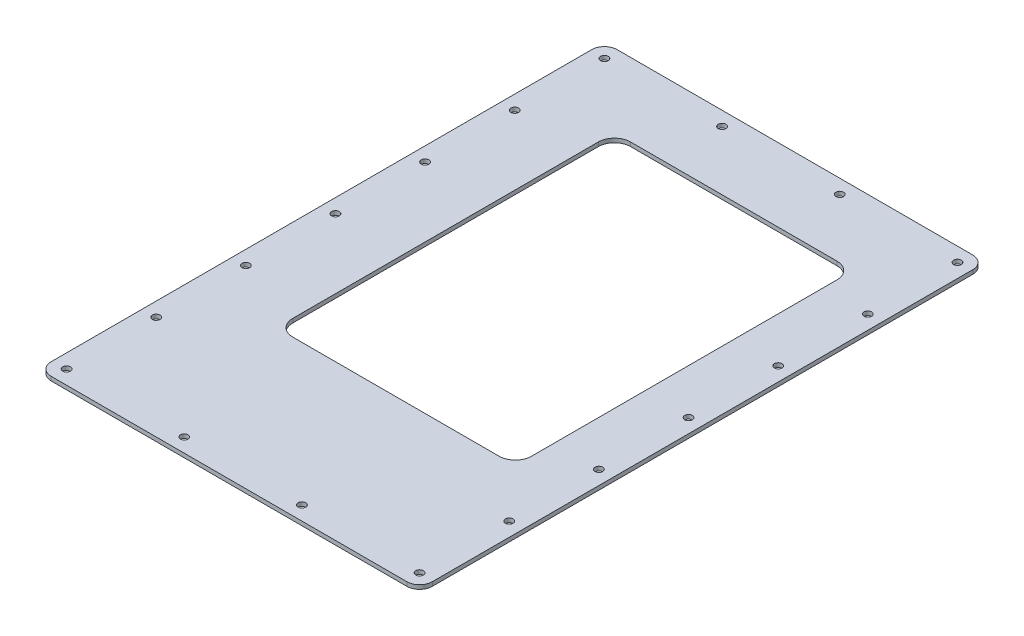
SolidWorks part; units mm, degrees
material "5052-H32"
ref_plane "Front Plane" through (0, 0, 0) normal (0, 0, 1) x (1, 0, 0)
ref_plane "Top Plane" through (0, 0, 0) normal (0, 1, 0) x (1, 0, 0)
ref_plane "Right Plane" through (0, 0, 0) normal (1, 0, 0) x (0, 0, -1)
sketch "Sketch9" plane through (0, 0, 0) normal (0, 1, 0) x (1, 0, 0)
  line L0 (-149.5, 0) -> (-149.5, 444)
  line L13 (-149.5, 444) -> (149.5, 444)
  line L14 (103.1625, 121.4438) -> (-84.1625, 121.4438)
  line L19 (149.5, 444) -> (149.5, 0)
  line L20 (103.1625, 121.4438) -> (103.1625, 386.5563)
  line L21 (103.1625, 386.5563) -> (-84.1625, 386.5563)
  line L22 (-84.1625, 121.4438) -> (-84.1625, 386.5563)
  line L23 (103.1625, 254) -> (-84.1625, 254) construction
  line L24 (9.5, 386.5562) -> (9.5, 121.4438) construction
  line L25 (-149.5, 0) -> (149.5, 0)
  point P8 (0, 0)
  point P19 (0, 0)
  dimension "D3" = 265.1125
  dimension "D4" = 187.325
  dimension "D1" = 299
  dimension "D2" = 444
  dimension "D6" = 140
  dimension "D5" = 190
extrude "Boss-Extrude7" add sketch "Sketch9" along normal blind 3.175 separate body contours L0 L25 L19 L13 L14 L22 L21 L20 region at (-144.1471, 0, -222)
fillet "Fillet4" radius 10 4 edges at (-149.5, 1.5875, -444) (149.5, 1.5875, -444) (-149.5, 1.5875, 0) (149.5, 1.5875, 0)
fillet "Fillet5" radius 12.7 4 edges at (-84.1625, 1.5875, -121.4438) (103.1625, 1.5875, -121.4438) (103.1625, 1.5875, -386.5563) (-84.1625, 1.5875, -386.5563)
sketch "Sketch10" plane through (0, 3.175, 0) normal (0, 1, 0) x (1, 0, 0)
  line L0 (-149.5, 10) -> (-149.5, 434) construction
  line L1 (-139.5, 0) -> (139.5, 0) construction
  circle A0 centre (-138.5, 11) radius 3
  circle A1 centre (-46.1667, 11) radius 3
  circle A2 centre (46.1667, 11) radius 3
  circle A3 centre (138.5, 11) radius 3
  circle A56 centre (-138.5, 81.3333) radius 3
  circle A57 centre (-138.5, 151.6667) radius 3
  circle A58 centre (-138.5, 222) radius 3
  circle A59 centre (-138.5, 292.3333) radius 3
  circle A60 centre (-138.5, 362.6667) radius 3
  circle A61 centre (-138.5, 433) radius 3
  circle A68 centre (138.5, 81.3333) radius 3
  circle A72 centre (138.5, 151.6667) radius 3
  circle A76 centre (138.5, 222) radius 3
  circle A80 centre (138.5, 292.3333) radius 3
  circle A84 centre (138.5, 362.6667) radius 3
  circle A86 centre (-46.1667, 433) radius 3
  circle A87 centre (46.1667, 433) radius 3
  circle A88 centre (138.5, 433) radius 3
  circle A102 centre (-46.1667, 81.3333) radius 3 [skipped]
  circle A103 centre (46.1667, 81.3333) radius 3 [skipped]
  circle A104 centre (-46.1667, 151.6667) radius 3 [skipped]
  circle A105 centre (46.1667, 151.6667) radius 3 [skipped]
  circle A106 centre (-46.1667, 222) radius 3 [skipped]
  circle A107 centre (46.1667, 222) radius 3 [skipped]
  circle A108 centre (-46.1667, 292.3333) radius 3 [skipped]
  circle A109 centre (46.1667, 292.3333) radius 3 [skipped]
  circle A110 centre (-46.1667, 362.6667) radius 3 [skipped]
  circle A111 centre (46.1667, 362.6667) radius 3 [skipped]
  dimension "D1" = 6
  dimension "D2" = 11
  dimension "D3" = 11
  dimension "D6" = 70.3333
  dimension "D7" = 92.3333
  dimension "D4" = 4
extrude "Cut-Extrude1" cut sketch "Sketch10" against normal up to surface (3.175 mm away) up to face at (9.5, 0, -254)
equation "\"W\"= 255"
equation "\"L\"= 400"
equation "\"Offset\"= 30"
equation "\"H\"= 110"
equation "\"Compartment Width\"= 80"
equation "\"T\"= 4.7625 * 2 / 3"
equation "\"Inside Fillet Radius\"= 5.55625"
equation "\"Hole\"=15"
equation "\"Wheel to Wall\"= 43"
equation "\"D1@Sketch9\"=\"W\"+44"
equation "\"D2@Sketch9\"=\"L\"+44"
equation "\"D6@Sketch10\"=(\"L\"+22)/6"
equation "\"D7@Sketch10\"=(\"W\"+22)/3"
equation "\"D5@Sketch9\"=(\"L\"/2+20)-\"Offset\""
